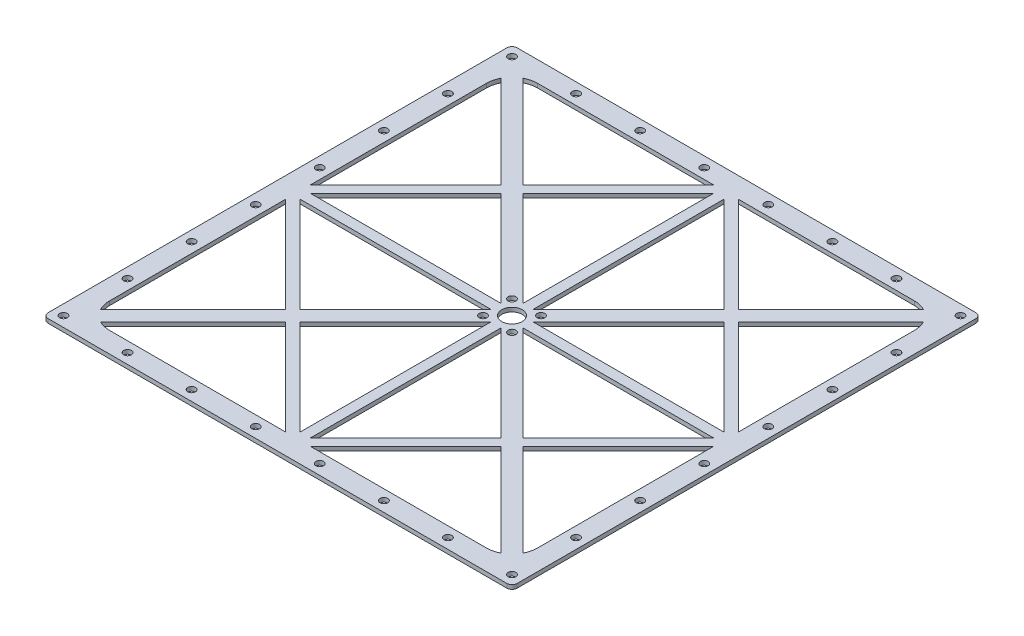
SolidWorks part; units mm, degrees
ref_plane "Front Plane" through (0, 0, 0) normal (0, 0, 1) x (1, 0, 0)
ref_plane "Top Plane" through (0, 0, 0) normal (0, 1, 0) x (1, 0, 0)
ref_plane "Right Plane" through (0, 0, 0) normal (1, 0, 0) x (0, 0, -1)
sketch "Sketch1" plane through (0, 0, 0) normal (0, 1, 0) x (1, 0, 0)
  line L0 (0, 183) -> (183, 0) construction
  line L1 (0, 0) -> (183, 0)
  line L2 (0, 0) -> (0, 183)
  line L3 (0, 183) -> (183, 183)
  line L4 (183, 0) -> (183, 183)
  circle A0 centre (91.5, 91.5) radius 90 construction
  circle A1 centre (91.5, 91.5) radius 8 construction
  circle A6 centre (91.5, 91.5) radius 13.5 construction
  circle A7 centre (85.8431, 97.1569) radius 1.5
  circle A8 centre (97.1569, 97.1569) radius 1.5
  circle A9 centre (97.1569, 85.8431) radius 1.5
  circle A10 centre (85.8431, 85.8431) radius 1.5
  point P8 (85.8431, 97.1569)
  point P19 (91.5, 91.5)
  point P22 (91.5, 91.5)
  dimension "D2" = 180
  dimension "D3" = 16
  dimension "D4" = 3
  dimension "D6" = 27
  dimension "D1" = 183
  dimension "D5" = 4
extrude "Boss-Extrude1" add sketch "Sketch1" along normal blind 1.6
sketch "Sketch2" plane through (0, 1.6, 0) normal (0, 1, 0) x (1, 0, 0)
  line L0 (9.1333, 169.624) -> (169.624, 9.1333)
  line L1 (18, 175) -> (165, 175)
  line L2 (8, 165) -> (8, 18)
  line L3 (18, 8) -> (165, 8)
  line L4 (175, 165) -> (175, 18)
  line L5 (13.376, 173.8667) -> (173.8667, 13.376)
  line L6 (8, 91.5) -> (175, 91.5) construction
  line L7 (17.3202, 169.9224) -> (13.0776, 165.6798) construction
  line L8 (91.5, 175) -> (91.5, 8) construction
  line L9 (173.8667, 169.624) -> (13.376, 9.1333)
  line L10 (0, 183) -> (183, 0) construction
  line L11 (183, 183) -> (0, 0) construction
  line L12 (164.9546, 169.1972) -> (169.1972, 164.9546) construction
  line L13 (169.624, 173.8667) -> (9.1333, 13.376)
  line L15 (0, 183) -> (0, 0) construction
  line L18 (0, 0) -> (183, 0) construction
  arc A0 (8, 165) -> (18, 175) centre (18, 165) cw
  arc A1 (165, 175) -> (175, 165) centre (165, 165) cw
  arc A2 (175, 18) -> (165, 8) centre (165, 18) cw
  arc A3 (18, 8) -> (8, 18) centre (18, 18) cw
  point P1 (175, 91.5)
  point P2 (91.5, 175)
  point P16 (15.1989, 167.8011)
  point P18 (8, 91.5)
  point P31 (91.5, 91.5)
  point P42 (91.5, 91.5)
  point P45 (167.0759, 167.0759)
  dimension "D3" = 6
  dimension "D4" = 8
  dimension "D2" = 10
  dimension "D5" = 10
  dimension "D6" = 10
  dimension "D7" = 10
  dimension "D1" = 8
extrude "Cut-Extrude1" cut sketch "Sketch2" against normal blind 2 contours A1 L1 A0 L5 L13 | A3 L13 L0 A0 L2 | A3 L3 A2 L0 L9 | A2 L4 A1 L9 L5 region at (34.4386, 1.6, -91.5) region at (91.5, 1.6, -148.5614) region at (91.5, 1.6, -34.4386) region at (148.5614, 1.6, -91.5)
fillet "Fillet1" radius 2 4 edges at (0, 0.8, 0) (183, 0.8, 0) (183, 0.8, -183) (0, 0.8, -183)
sketch "Sketch3" plane through (0, 1.6, 0) normal (0, 1, 0) x (1, 0, 0)
  line L0 (0.5858, 182.4142) -> (182.4142, 0.5858) construction
  circle A0 centre (4, 179) radius 1.5
  arc A1 (2, 183) -> (0, 181) centre (2, 181) ccw construction
  arc A2 (181, 0) -> (183, 2) centre (181, 2) ccw construction
  circle A3 centre (179, 179) radius 1.5
  circle A4 centre (179, 4) radius 1.5
  circle A5 centre (4, 4) radius 1.5
  point P14 (91.5, 91.5)
  point P20 (91.5, 91.5)
  dimension "D1" = 3
  dimension "D2" = 175
  dimension "D3" = 4
extrude "Cut-Extrude2" cut sketch "Sketch3" against normal through all
sketch "Sketch4" plane through (0, 1.6, 0) normal (0, 1, 0) x (1, 0, 0)
  line L1 (93.5, 89.5) -> (175, 89.5)
  line L2 (93.5, 93.5) -> (93.5, 175)
  line L7 (17.7285, 161.0289) -> (21.9711, 165.2715) construction
  line L8 (9.1333, 169.624) -> (87.2574, 91.5) construction
  line L9 (13.376, 173.8667) -> (91.5, 95.7426) construction
  line L10 (89.5, 175) -> (89.5, 93.5)
  line L11 (18, 175) -> (165, 175) construction
  line L12 (18, 8) -> (165, 8) construction
  line L13 (89.5, 8) -> (93.5, 8)
  line L14 (93.5, 8) -> (93.5, 89.5)
  line L15 (93.5, 175) -> (89.5, 175)
  line L16 (8, 91.5) -> (175, 91.5) construction
  line L17 (8, 165) -> (8, 18) construction
  line L18 (175, 165) -> (175, 18) construction
  line L19 (89.5, 111.6709) -> (93.5, 111.6709) construction
  line L20 (175, 93.5) -> (93.5, 93.5)
  line L21 (8, 93.5) -> (8, 89.5)
  line L22 (8, 89.5) -> (89.5, 89.5)
  line L23 (175, 89.5) -> (175, 93.5)
  line L24 (89.5, 93.5) -> (8, 93.5)
  line L25 (89.5, 89.5) -> (89.5, 8)
  point P22 (91.5, 111.6709)
  point P25 (91.5, 91.5)
  point P30 (91.5, 91.5)
  dimension "D1" = 4
  dimension "D2" = 2
extrude "Boss-Extrude2" add sketch "Sketch4" against normal up to surface (1.6 mm away) up to face at (4, 0, -2.5)
sketch "Sketch8" plane through (0, 1.6, 0) normal (0, 1, 0) x (1, 0, 0)
  line L0 (89.5, 97.7426) -> (93.5, 85.2574) construction
  circle A0 centre (91.5, 91.5) radius 4
  dimension "D1" = 8
extrude "Cut-Extrude4" cut sketch "Sketch8" against normal through all
sketch "Sketch6" plane through (0, 1.6, 0) normal (0, 1, 0) x (1, 0, 0)
  line L0 (8, 89.5) -> (89.5, 8) construction
  line L1 (10.8284, 89.5) -> (89.5, 10.8284)
  line L2 (8, 89.5) -> (85.2574, 89.5) construction
  line L3 (89.5, 85.2574) -> (89.5, 8) construction
  line L4 (89.5, 10.8284) -> (89.5, 8)
  line L5 (89.5, 8) -> (86.6716, 8)
  line L6 (18, 8) -> (89.5, 8) construction
  line L7 (86.6716, 8) -> (8, 86.6716)
  line L8 (8, 89.5) -> (8, 18) construction
  line L9 (8, 86.6716) -> (8, 89.5)
  line L10 (8, 89.5) -> (10.8284, 89.5)
  line L11 (20.8163, 79.5121) -> (17.9879, 76.6837) construction
  line L12 (0, 91.5) -> (183, 91.5) construction
  line L21 (0, 181) -> (0, 2) construction
  line L22 (183, 2) -> (183, 181) construction
  line L29 (91.5, 183) -> (91.5, 0) construction
  line L30 (181, 183) -> (2, 183) construction
  line L37 (2, 0) -> (181, 0) construction
  line L38 (20.8163, 103.4879) -> (17.9879, 106.3163) construction
  line L39 (8, 93.5) -> (89.5, 175) construction
  line L40 (8, 93.5) -> (10.8284, 93.5)
  line L41 (8, 96.3284) -> (8, 93.5)
  line L42 (86.6716, 175) -> (8, 96.3284)
  line L43 (89.5, 175) -> (86.6716, 175)
  line L44 (89.5, 172.1716) -> (89.5, 175)
  line L45 (10.8284, 93.5) -> (89.5, 172.1716)
  line L46 (175, 93.5) -> (93.5, 175) construction
  line L47 (162.1837, 103.4879) -> (165.0121, 106.3163) construction
  line L48 (162.1837, 79.5121) -> (165.0121, 76.6837) construction
  line L49 (175, 89.5) -> (93.5, 8) construction
  line L50 (172.1716, 93.5) -> (93.5, 172.1716)
  line L51 (93.5, 172.1716) -> (93.5, 175)
  line L52 (93.5, 175) -> (96.3284, 175)
  line L53 (96.3284, 175) -> (175, 96.3284)
  line L54 (175, 96.3284) -> (175, 93.5)
  line L55 (175, 93.5) -> (172.1716, 93.5)
  line L56 (175, 89.5) -> (172.1716, 89.5)
  line L57 (175, 86.6716) -> (175, 89.5)
  line L58 (96.3284, 8) -> (175, 86.6716)
  line L59 (93.5, 8) -> (96.3284, 8)
  line L60 (93.5, 10.8284) -> (93.5, 8)
  line L61 (172.1716, 89.5) -> (93.5, 10.8284)
  point P13 (19.4021, 78.0979)
  dimension "D1" = 4
extrude "Boss-Extrude4" add sketch "Sketch6" against normal up to surface (1.6 mm away) up to face at (91.5, 0, -87.5)
sketch "Sketch7" plane through (0, 1.6, 0) normal (0, 1, 0) x (1, 0, 0)
  line L0 (4, 177.5) -> (4, 4) construction
  line L1 (91.5, 183) -> (91.5, 0) construction
  line L2 (181, 183) -> (2, 183) construction
  line L3 (2, 0) -> (181, 0) construction
  line L4 (177.5, 179) -> (4, 179) construction
  line L5 (179, 5.5) -> (179, 179) construction
  line L6 (5.5, 4) -> (179, 4) construction
  circle A0 centre (4, 179) radius 1.5 construction
  circle A1 centre (29, 179) radius 1.5
  circle A2 centre (4, 29) radius 1.5
  circle A3 centre (4, 54) radius 1.5
  circle A4 centre (4, 79) radius 1.5
  circle A5 centre (4, 104) radius 1.5
  circle A6 centre (4, 129) radius 1.5
  circle A7 centre (4, 154) radius 1.5
  circle A8 centre (54, 179) radius 1.5
  circle A9 centre (79, 179) radius 1.5
  circle A10 centre (104, 179) radius 1.5
  circle A11 centre (129, 179) radius 1.5
  circle A12 centre (154, 179) radius 1.5
  circle A13 centre (179, 154) radius 1.5
  circle A14 centre (179, 129) radius 1.5
  circle A15 centre (179, 104) radius 1.5
  circle A16 centre (179, 79) radius 1.5
  circle A17 centre (179, 54) radius 1.5
  circle A18 centre (179, 29) radius 1.5
  circle A19 centre (154, 4) radius 1.5
  circle A20 centre (129, 4) radius 1.5
  circle A21 centre (104, 4) radius 1.5
  circle A22 centre (79, 4) radius 1.5
  circle A23 centre (54, 4) radius 1.5
  circle A24 centre (29, 4) radius 1.5
  point P4 (91.5, 91.5)
  point P8 (4, 4)
  point P70 (91.5, 91.5)
  dimension "D1" = 3
  dimension "D2" = 25
  dimension "D4" = 25
  dimension "D3" = 6
extrude "Cut-Extrude3" cut sketch "Sketch7" against normal up to surface (1.6 mm away) up to face at (150.9743, 0, -82.0571)
